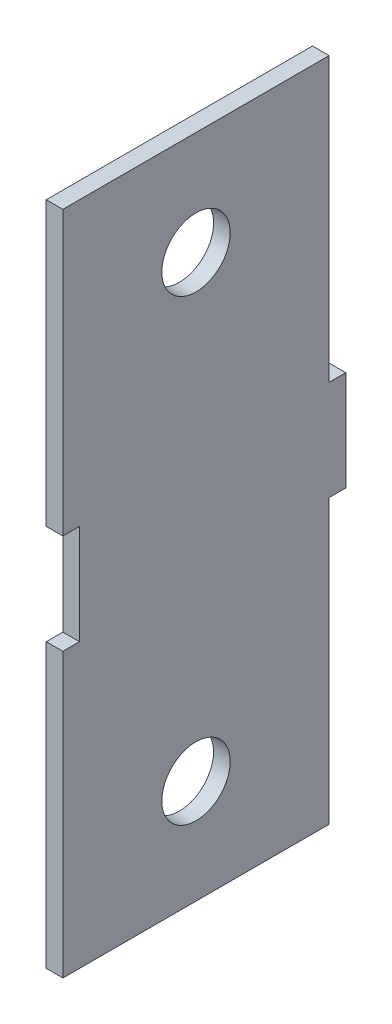
SolidWorks part; units mm, degrees
material "AISI 4130 Steel, annealed at 865C"
ref_plane "Front Plane" through (0, 0, 0) normal (0, 0, 1) x (1, 0, 0)
ref_plane "Top Plane" through (0, 0, 0) normal (0, 1, 0) x (1, 0, 0)
ref_plane "Right Plane" through (0, 0, 0) normal (1, 0, 0) x (0, 0, -1)
sketch "Sketch2" plane through (0, 0, 0) normal (1, 0, 0) x (0, 0, -1)
  line L0 (0, 21.844) -> (0, -21.844) construction
  line L1 (-12.7, -31.75) -> (12.7, -31.75)
  line L2 (-12.7, -31.75) -> (-12.7, 31.75)
  line L3 (-12.7, 31.75) -> (12.7, 31.75)
  line L4 (12.7, -31.75) -> (12.7, 31.75)
  line L5 (-12.7, -31.75) -> (12.7, 31.75) construction
  line L6 (-12.7, 31.75) -> (12.7, -31.75) construction
  circle A0 centre (0, 21.844) radius 3.2639
  circle A1 centre (0, -21.844) radius 3.2639
  point P0 (0, 0)
  point P6 (0, 0)
  point P7 (0, 0)
  point P13 (0, 0)
  dimension "D3" = 6.5278
  dimension "D4" = 6.5278
  dimension "D1" = 25.4
  dimension "D2" = 63.5
  dimension "D5" = 90
  dimension "D6" = 43.688
extrude "Boss-Extrude1" add sketch "Sketch2" along normal blind 1.5875
sketch "Sketch3" plane through (1.5875, 0, 0) normal (1, 0, 0) x (0, 0, -1)
  line L0 (-12.7, 0) -> (12.7, 0) construction
  line L1 (-12.7, 31.75) -> (-12.7, -31.75) construction
  line L2 (12.7, -31.75) -> (12.7, 31.75) construction
  line L4 (-12.7, 4.7625) -> (-11.1125, 4.7625)
  line L5 (-12.7, 4.7625) -> (-12.7, -4.7625)
  line L6 (-12.7, -4.7625) -> (-11.1125, -4.7625)
  line L7 (-11.1125, 4.7625) -> (-11.1125, -4.7625)
  line L8 (12.7, 4.7625) -> (14.2875, 4.7625)
  line L9 (12.7, 4.7625) -> (12.7, -4.7625)
  line L10 (12.7, -4.7625) -> (14.2875, -4.7625)
  line L11 (14.2875, 4.7625) -> (14.2875, -4.7625)
  point P14 (-11.1125, 0)
  dimension "D1" = 9.525
  dimension "D2" = 1.5875
  dimension "D3" = 1.5875
extrude "Boss-Extrude2" add sketch "Sketch3" against normal blind 1.5875 contours L9 L8 L11 L10
extrude "Cut-Extrude1" cut sketch "Sketch3<4>" against normal blind 3.175 contours L7 L6 L5 L4
sketch "Sketch3<4>" plane through (1.5875, 0, 0) normal (1, 0, 0) x (0, 0, -1) same geometry as "Sketch3"
